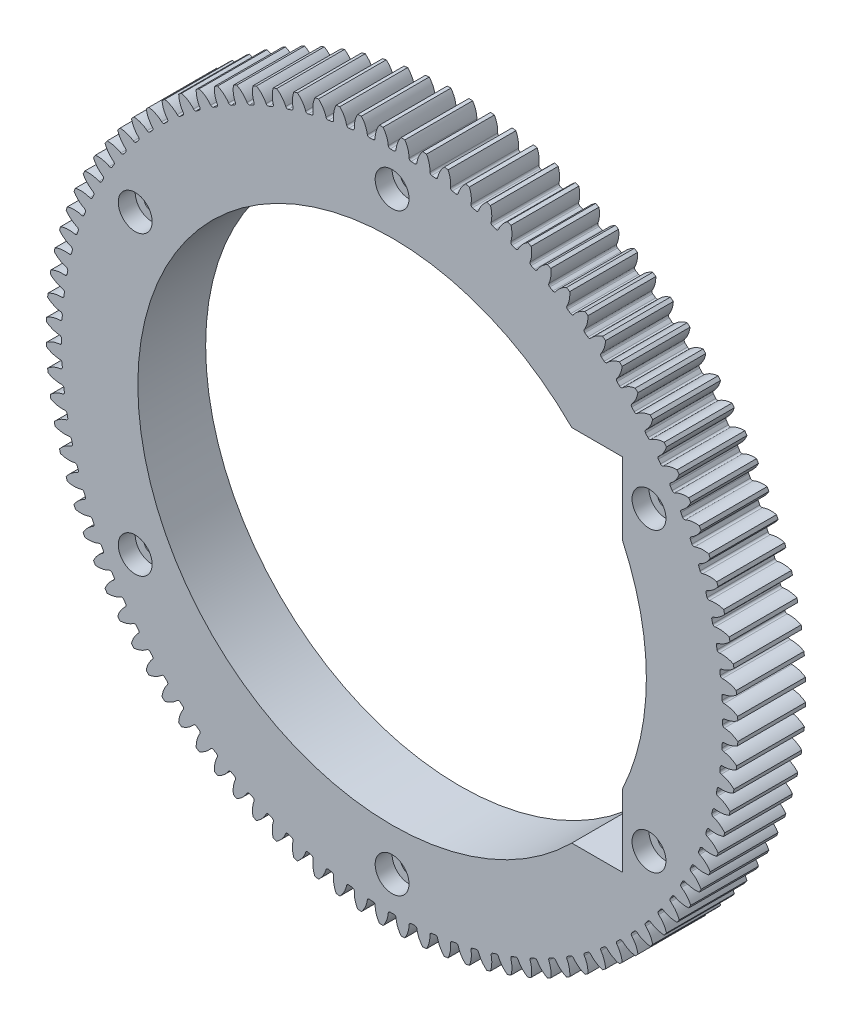
SolidWorks part; units mm, degrees
ref_plane "Front Plane" through (0, 0, 0) normal (0, 0, 1) x (1, 0, 0)
ref_plane "Top Plane" through (0, 0, 0) normal (0, 1, 0) x (1, 0, 0)
ref_plane "Right Plane" through (0, 0, 0) normal (1, 0, 0) x (0, 0, -1)
sketch "Sketch2" plane through (0, 0, 0) normal (0, 0, 1) x (1, 0, 0)
  circle A0 centre (0, 0) radius 100 construction
  circle A1 centre (0, 0) radius 102
  dimension "D1" = 200
  dimension "D2" = 204
extrude "Boss-Extrude1" add sketch "Sketch2" along normal mid plane 20 contours A1
sketch "Sketch3" plane through (0, 0, 0) normal (0, 0, 1) x (1, 0, 0)
  line L0 (0, 102) -> (0, 0) construction
  line L1 (0, 0) -> (6.4046, 101.7987) construction
  line L2 (0, 0) -> (3.2039, 101.9497) construction
  line L3 (-1.1162, 97.4936) -> (0, 0) construction
  line L4 (-1.5707, 99.9877) -> (1.5707, 99.9877) construction
  line L5 (1.5707, 99.9877) -> (4.7106, 99.889) construction
  line L6 (-2.2938, 101.9742) -> (0, 95.6721) construction
  circle A0 centre (0, 0) radius 98 construction
  arc A1 (1.1162, 97.4936) -> (-1.1162, 97.4936) centre (0, 0) ccw
  circle A2 centre (0, 0) radius 102 construction
  circle A3 centre (0, 0) radius 100 construction
  arc A4 (-2.6485, 101.9656) -> (-1.1162, 97.4936) centre (-8.6604, 97.4072) cw
  arc A5 (2.6485, 101.9656) -> (1.1162, 97.4936) centre (8.6604, 97.4072) ccw
  arc A6 (2.6485, 101.9656) -> (-2.6485, 101.9656) centre (0, 0) ccw
  dimension "D4" = 200
  dimension "D1" = 3.6
  dimension "D2" = 4
  dimension "D3" = 4.5
  dimension "D5" = 20
extrude "Cut-Extrude1" cut sketch "Sketch3" against normal through all both and the other way through all
fillet "Fillet1" radius 0.6 2 edges at (1.1162, 97.4936, 0) (-1.1162, 97.4936, 0)
ref_axis "Axis1" through (0, 0, -11) along (0, 0, 1)
pattern_circular "CirPattern1" count 100 over 360 about axis through (0, 0, -11) along (0, 0, 1) of "Cut-Extrude1", "Fillet1"
sketch "Sketch4" plane through (0, 0, -10) normal (0, 0, -1) x (-1, 0, 0)
  circle A0 centre (0, 0) radius 5
  dimension "D1" = 10
extrude "Cut-Extrude3" cut sketch "Sketch4" against normal blind 10
sketch "Sketch5" plane through (0, 0, 10) normal (0, 0, 1) x (1, 0, 0)
  circle A0 centre (0, 0) radius 75
  circle A1 centre (0, 0) radius 87.5 construction
  circle A2 centre (0, 87.5) radius 2.5
  circle A3 centre (75.7772, 43.75) radius 2.5
  circle A4 centre (75.7772, -43.75) radius 2.5
  circle A5 centre (0, -87.5) radius 2.5
  circle A6 centre (-75.7772, -43.75) radius 2.5
  circle A7 centre (-75.7772, 43.75) radius 2.5
  point P18 (0, 0)
  dimension "D1" = 5
  dimension "D2" = 175
  dimension "D3" = 150
  dimension "D4" = 6
extrude "Cut-Extrude4" cut sketch "Sketch5" against normal through all
sketch "Sketch6" plane through (0, 0, 10) normal (0, 0, 1) x (1, 0, 0)
  circle A0 centre (0, 87.5) radius 5
  circle A1 centre (75.7772, 43.75) radius 5
  circle A2 centre (75.7772, -43.75) radius 5
  circle A3 centre (0, -87.5) radius 5
  circle A4 centre (-75.7772, -43.75) radius 5
  circle A5 centre (-75.7772, 43.75) radius 5
  point P16 (0, 0)
  dimension "D1" = 10
  dimension "D2" = 6
extrude "Cut-Extrude5" cut sketch "Sketch6" against normal blind 5
sketch "Sketch7" plane through (0, 0, 10) normal (0, 0, 1) x (1, 0, 0)
  line L1 (-53, 67.5) -> (53, 67.5) construction
  line L2 (-53, 67.5) -> (-53, -67.5) construction
  line L3 (-53, -67.5) -> (53, -67.5) construction
  line L4 (53, 67.5) -> (53, -67.5) construction
  line L5 (-53, 67.5) -> (53, -67.5) construction
  line L6 (-53, -67.5) -> (53, 67.5) construction
  line L7 (53, 53.066) -> (68, 53.066)
  line L8 (53, 53.066) -> (53, -53.066)
  line L9 (53, -53.066) -> (68, -53.066)
  line L10 (68, 53.066) -> (68, -53.066)
  circle A0 centre (0, 0) radius 75 construction
  point P0 (0, 0)
  point P12 (0, 0)
  dimension "D3" = 150
  dimension "D1" = 106
  dimension "D2" = 135
  dimension "D4" = 15
extrude "Cut-Extrude6" cut sketch "Sketch7" against normal blind 20
equation "\"Module\"= 2"
equation "\"Number of teeth\"= 100"
equation "\"pressure angle\"= 20"
equation "\"D1@Sketch2\"=\"Module\"*\"Number of teeth\""
equation "\"D2@Sketch2\"=(\"Number of teeth\"+2) *\"Module\""
equation "\"D1@Sketch3\"=360 /\"Number of teeth\""
equation "\"D2@Sketch3\"=\"Module\"*2"
equation "\"D3@Sketch3\"=\"Module\" *if( \"Module\"=> 1.25,2.25,2.4)"
equation "\"D5@Sketch3\"=\"pressure angle\""
equation "\"D4@Sketch3\"=\"Module\"*\"Number of teeth\""
equation "\"D1@CirPattern1\"=\"Number of teeth\""
equation "\"D1@Fillet1\"=0.3 *\"Module\""
